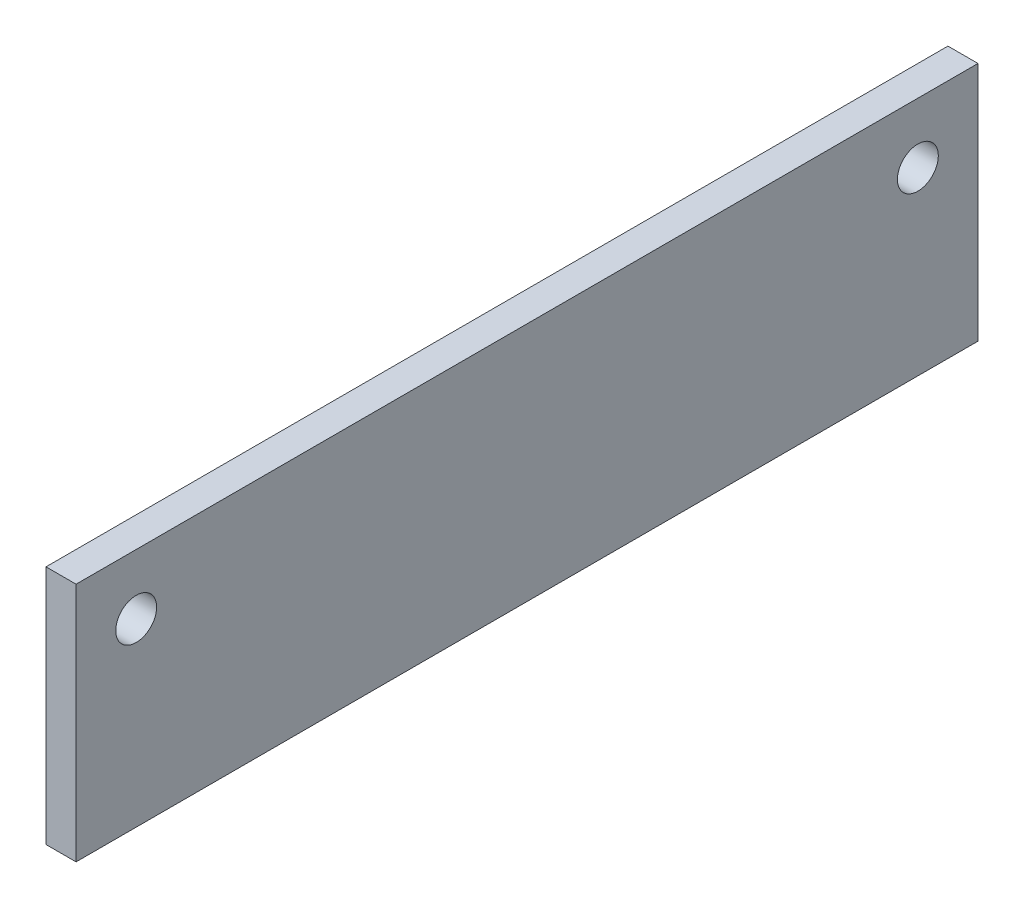
SolidWorks part; units mm, degrees
ref_plane "Front" through (0, 0, 0) normal (0, 0, 1) x (1, 0, 0)
ref_plane "Top" through (0, 0, 0) normal (0, 1, 0) x (1, 0, 0)
ref_plane "Right" through (0, 0, 0) normal (1, 0, 0) x (0, 0, -1)
sketch "Sketch1" plane through (0, 0, 0) normal (1, 0, 0) x (0, 0, -1)
  line L0 (37.5, 0) -> (-37.5, 0)
  line L1 (-37.5, 10) -> (37.5, 10)
  line L2 (-37.5, 10) -> (-37.5, -10)
  line L3 (-37.5, -10) -> (37.5, -10)
  line L4 (37.5, 10) -> (37.5, -10)
  line L5 (-37.5, 10) -> (37.5, -10) construction
  line L6 (-37.5, -10) -> (37.5, 10) construction
  line L7 (-37.5, 0) -> (-37.5, 10)
  line L8 (-37.5, 5) -> (37.5, 5)
  circle A0 centre (32.5, 5) radius 1.7
  circle A1 centre (-32.5, 5) radius 1.7
  point P0 (0, 0)
  dimension "D3" = 5
  dimension "D1" = 75
  dimension "D2" = 20
  dimension "D4" = 5
extrude "Boss-Extrude1" add sketch "Sketch1" along normal blind 2.5 contours A1 L8 A0 L4 L1 L2 | A1 L8 L7 L0 L4 A0 | L4 L0 L2 L3 region at (0, -5, 0) region at (0, 2.4559, 0) region at (0, 7.5441, 0)
